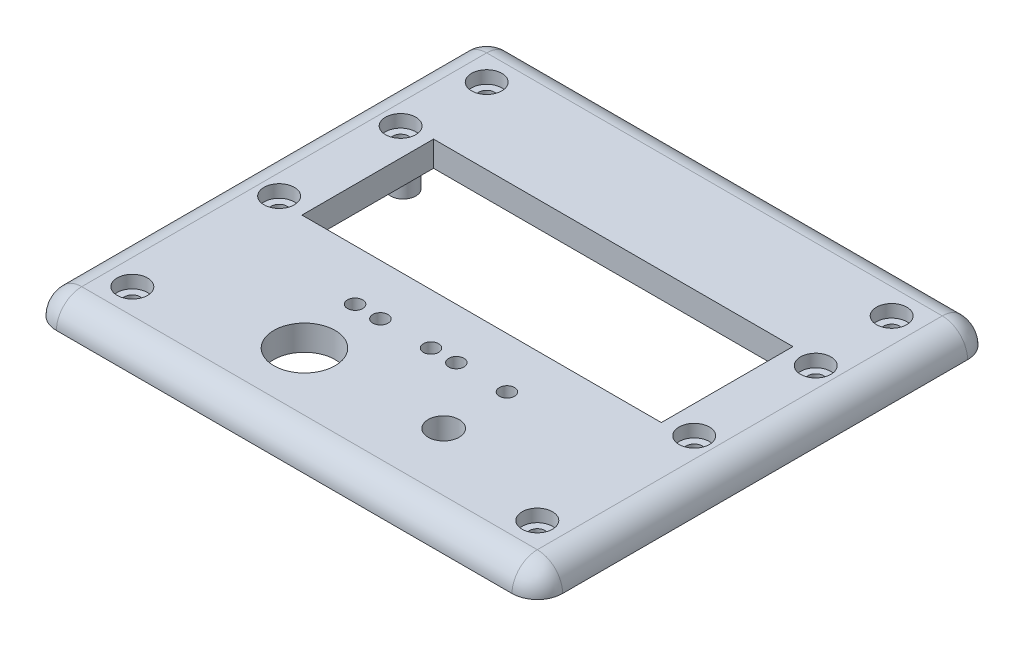
SolidWorks part; units mm, degrees
ref_plane "Front Plane" through (0, 0, 0) normal (0, 0, 1) x (1, 0, 0)
ref_plane "Top Plane" through (0, 0, 0) normal (0, 1, 0) x (1, 0, 0)
ref_plane "Right Plane" through (0, 0, 0) normal (1, 0, 0) x (0, 0, -1)
sketch "Sketch1" plane through (0, 0, 0) normal (0, 1, 0) x (1, 0, 0)
  line L1 (0, 0) -> (100, 0)
  line L2 (0, 0) -> (0, 90)
  line L3 (0, 90) -> (100, 90)
  line L4 (100, 0) -> (100, 90)
  dimension "D1" = 100
  dimension "D2" = 90
extrude "Boss-Extrude1" add sketch "Sketch1" along normal blind 5
fillet "Fillet1" radius 5 4 edges at (0, 2.5, -90) (0, 2.5, 0) (100, 2.5, -90) (100, 2.5, 0)
fillet "Fillet2" radius 5 8 edges at (1.4645, 5, -1.4645) (98.5355, 5, -88.5355) (98.5355, 5, -1.4645) (100, 5, -45) (50, 5, 0) (0, 5, -45) (1.4645, 5, -88.5355) (50, 5, -90)
sketch "Sketch2" plane through (0, 5, 0) normal (0, 1, 0) x (1, 0, 0)
  line L0 (90, 80) -> (10, 80) construction
  line L1 (10, 80) -> (10, 10) construction
  line L2 (10, 80) -> (5, 80) construction
  line L3 (5, 85) -> (5, 5) construction
  line L4 (5, 80) -> (5, 85) construction
  line L5 (90, 10) -> (95, 10) construction
  line L6 (95, 5) -> (95, 85) construction
  line L7 (95, 10) -> (95, 5) construction
  circle A0 centre (10, 80) radius 1.55
  circle A1 centre (10, 10) radius 1.55
  circle A2 centre (90, 10) radius 1.55
  circle A3 centre (90, 80) radius 1.55
  dimension "D1" = 3.1
  dimension "D2" = 80
  dimension "D3" = 70
extrude "Cut-Extrude1" cut sketch "Sketch2" against normal blind 10
sketch "Sketch3" plane through (0, 5, 0) normal (0, 1, 0) x (1, 0, 0)
  circle A0 centre (10, 80) radius 3
  circle A1 centre (90, 80) radius 3
  circle A2 centre (90, 10) radius 3
  circle A3 centre (10, 10) radius 3
  dimension "D1" = 6
extrude "Cut-Extrude2" cut sketch "Sketch3" against normal blind 2.5
sketch "Sketch4" plane through (0, 5, 0) normal (0, 1, 0) x (1, 0, 0)
  line L0 (85.5, 52) -> (95, 52) construction
  line L1 (65, 29) -> (95, 29) construction
  line L3 (95, 5) -> (95, 85) construction
  line L4 (35, 29) -> (5, 29) construction
  line L5 (5, 85) -> (5, 5) construction
  line L6 (14.5, 65) -> (85.5, 65)
  line L7 (14.5, 65) -> (14.5, 39)
  line L8 (14.5, 39) -> (85.5, 39)
  line L9 (85.5, 65) -> (85.5, 39)
  line L10 (14.5, 52) -> (5, 52) construction
  line L11 (95, 85) -> (5, 85) construction
  circle A0 centre (35, 29) radius 1.5
  circle A1 centre (40, 29) radius 1.5
  circle A2 centre (50, 29) radius 1.5
  circle A3 centre (55, 29) radius 1.5
  circle A4 centre (65, 29) radius 1.5
  dimension "D1" = 3
  dimension "D2" = 5
  dimension "D3" = 5
  dimension "D4" = 10
  dimension "D5" = 10
  dimension "D6" = 10
  dimension "D7" = 71
  dimension "D8" = 26
  dimension "D9" = 20
extrude "Cut-Extrude3" cut sketch "Sketch4" against normal through all
sketch "Sketch5" plane through (0, 0, 0) normal (0, -1, 0) x (1, 0, 0)
  line L0 (85.5, -52) -> (92.5, -52) construction
  line L1 (7.5, -37) -> (92.5, -37) construction
  line L2 (7.5, -37) -> (7.5, -67) construction
  line L3 (7.5, -67) -> (92.5, -67) construction
  line L4 (92.5, -37) -> (92.5, -67) construction
  line L5 (85.5, -39) -> (85.5, -65) construction
  line L6 (14.5, -52) -> (7.5, -52) construction
  line L7 (14.5, -65) -> (14.5, -39) construction
  line L8 (9, -40) -> (9, -37) construction
  line L9 (9, -64) -> (9, -67) construction
  circle A0 centre (9, -40) radius 1.5
  circle A1 centre (9, -64) radius 1.5
  circle A2 centre (91, -64) radius 1.5
  circle A3 centre (91, -40) radius 1.5
  dimension "D3" = 3
  dimension "D1" = 85
  dimension "D2" = 30
  dimension "D4" = 24
extrude "Cut-Extrude4" cut sketch "Sketch5" against normal through all
sketch "Sketch8" plane through (0, 0, 0) normal (0, -1, 0) x (1, 0, 0)
  line L0 (95, -90) -> (5, -90) construction
  line L1 (9, -40) -> (0, -40) construction
  line L2 (0, -85) -> (0, -5) construction
  line L5 (100, -5) -> (100, -85) construction
  line L6 (100, -64.5) -> (91, -64.5) construction
  circle A4 centre (9, -40) radius 2.5
  circle A5 centre (91, -40) radius 2.5
  circle A6 centre (91, -64.5) radius 2.5
  circle A7 centre (9, -64.5) radius 2.5
  circle A8 centre (91, -40) radius 1.5 construction
  dimension "D1" = 5
  dimension "D4" = 25.5
extrude "Boss-Extrude3" add sketch "Sketch8" along normal blind 6
sketch "Sketch6" plane through (0, 5, 0) normal (0, 1, 0) x (1, 0, 0)
  circle A0 centre (9, 40) radius 3
  circle A1 centre (9, 64) radius 3
  circle A2 centre (91, 64) radius 3
  circle A3 centre (91, 40) radius 3
  dimension "D1" = 6
extrude "Cut-Extrude5" cut sketch "Sketch6" against normal blind 2.5
sketch "Sketch10" plane through (0, 0, 0) normal (0, 1, 0) x (1, 0, 0)
  circle A0 centre (9, 64) radius 1.55
  circle A1 centre (9, 40) radius 1.55
  circle A2 centre (91, 40) radius 1.55
  circle A3 centre (91, 64) radius 1.55
  dimension "D1" = 3.1
extrude "Cut-Extrude7" cut sketch "Sketch10" against normal through all both and the other way through all
sketch "Sketch11" plane through (0, 5, 0) normal (0, 1, 0) x (1, 0, 0)
  line L0 (65, 16.5) -> (65, 29) construction
  line L1 (40, 29) -> (35, 29) construction
  line L2 (37.5, 29) -> (37.5, 16.5) construction
  circle A0 centre (37.5, 16.5) radius 6.05
  circle A1 centre (65, 16.5) radius 3.05
  dimension "D1" = 12.1
  dimension "D2" = 6.1
  dimension "D3" = 12.5
extrude "Cut-Extrude8" cut sketch "Sketch11" against normal blind 5
